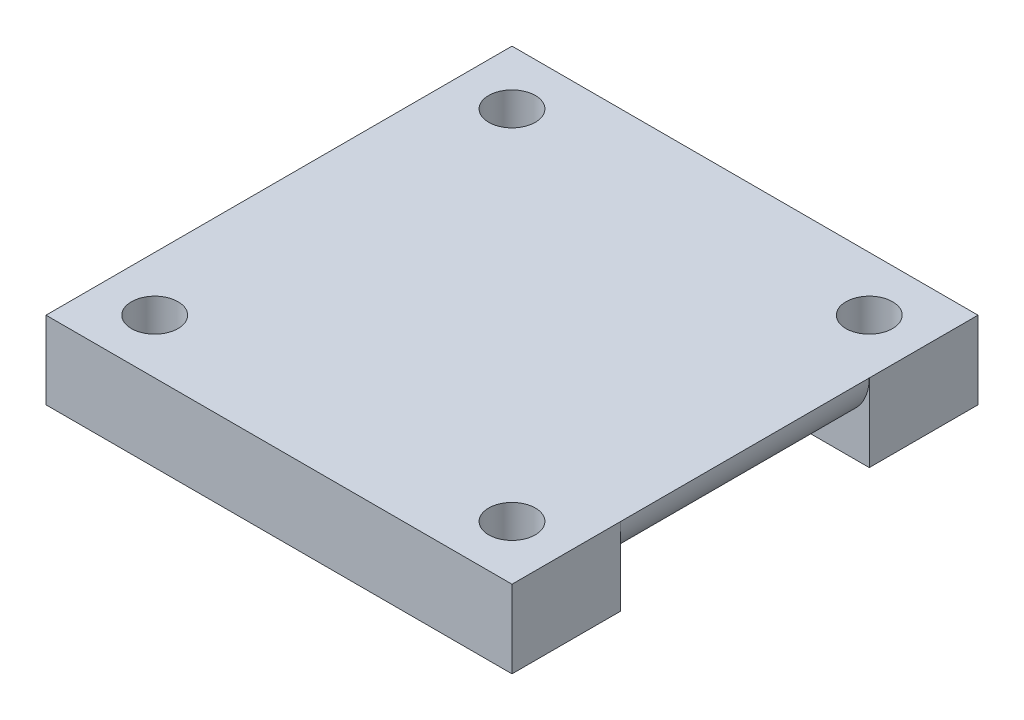
SolidWorks part; units mm, degrees
ref_plane "Front Plane" through (0, 0, 0) normal (0, 0, 1) x (1, 0, 0)
ref_plane "Top Plane" through (0, 0, 0) normal (0, 1, 0) x (1, 0, 0)
ref_plane "Right Plane" through (0, 0, 0) normal (1, 0, 0) x (0, 0, -1)
sketch "Sketch1" plane through (0, 0, 0) normal (0, 1, 0) x (1, 0, 0)
  line L0 (-15, 8) -> (15, 8)
  line L1 (-15, 15) -> (15, 15)
  line L2 (-15, 15) -> (-15, -15)
  line L3 (-15, -15) -> (15, -15)
  line L4 (15, 15) -> (15, -15)
  line L5 (-15, -8) -> (15, -8)
  line L6 (0, -55) -> (0, 55) construction
  line L7 (-55, 0) -> (55, 0) construction
  circle A0 centre (11.5, 11.5) radius 1.5
  circle A1 centre (-11.5, 11.5) radius 1.5
  circle A2 centre (11.5, -11.5) radius 1.5
  circle A3 centre (-11.5, -11.5) radius 1.5
  point P8 (15, 0)
  point P10 (0, 8)
  point P13 (0, 0)
  point P14 (0, 0)
  point P15 (0, 0)
  point P16 (11.2499, 10)
  dimension "D6" = 3
  dimension "D1" = 30
  dimension "D4" = 30
  dimension "D5" = 3.5
  dimension "D7" = 3.5
  dimension "D2" = 7
  dimension "D3" = 7
extrude "Boss-Extrude1" add sketch "Sketch1" along normal blind 5 contours L2 L5 L4 L0 | L4 L1 L2 L0 A0 A1 | L5 L2 L3 L4 A3 A2 region at (0, 0, -11.5) region at (0, 0, 0) region at (0, 0, 11.5)
extrude "Cut-Extrude1" cut sketch "Sketch1<3>" along normal blind 2 contours L2 L5 L4 L0 region at (0, 0, 0)
sketch "Sketch1<3>" plane through (0, 0, 0) normal (0, 1, 0) x (1, 0, 0) same geometry as "Sketch1"
fillet "Fillet1" radius 3 2 edges at (-15, 2, 0) (15, 2, 0)
